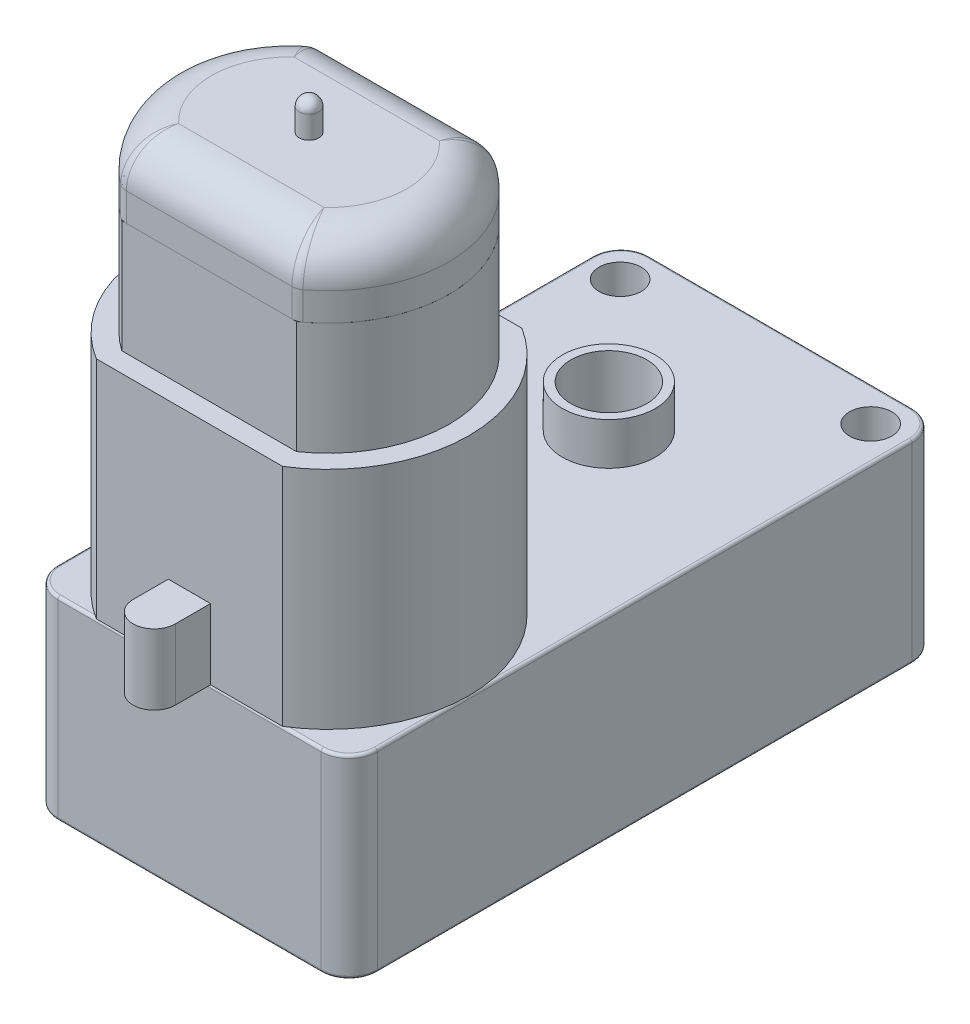
SolidWorks part; units mm, degrees
ref_plane "Front Plane" through (0, 0, 0) normal (0, 0, 1) x (1, 0, 0)
ref_plane "Top Plane" through (0, 0, 0) normal (0, 1, 0) x (1, 0, 0)
ref_plane "Right Plane" through (0, 0, 0) normal (1, 0, 0) x (0, 0, -1)
sketch "Sketch1" plane through (0, 0, 0) normal (0, 1, 0) x (1, 0, 0)
  line L1 (-11.35, -21) -> (11.35, -21)
  line L2 (-11.35, -21) -> (-11.35, 21)
  line L3 (-11.35, 21) -> (11.35, 21)
  line L4 (11.35, -21) -> (11.35, 21)
  line L5 (-11.35, -21) -> (11.35, 21) construction
  line L6 (-11.35, 21) -> (11.35, -21) construction
  point P0 (0, 0)
  dimension "D1" = 22.7
  dimension "D2" = 42
extrude "Boss-Extrude1" add sketch "Sketch1" along normal blind 13.8
sketch "Sketch2" plane through (0, 13.8, 0) normal (0, 1, 0) x (1, 0, 0)
  line L0 (-6.6178, -21) -> (6.6178, -21)
  line L1 (-11.35, -21) -> (11.35, -21) construction
  line L2 (-6.6178, -4) -> (6.6178, -4)
  line L3 (11.35, -21) -> (11.35, 21) construction
  line L4 (-11.35, 21) -> (-11.35, -21) construction
  arc A0 (6.6178, -4) -> (6.6178, -21) centre (1.35, -12.5) cw
  arc A1 (-6.6178, -4) -> (-6.6178, -21) centre (-1.35, -12.5) ccw
  point P8 (0, -4)
  point P9 (0, -21)
  dimension "D2" = 10
  dimension "D1" = 17
extrude "Boss-Extrude2" add sketch "Sketch2" along normal blind 16 separate body
sketch "Sketch3" plane through (0, 0, 0) normal (0, -1, 0) x (1, 0, 0)
  line L0 (11.35, -21) -> (-11.35, -21) construction
  circle A0 centre (0, -8.8) radius 2.7
  dimension "D1" = 5.4
  dimension "D2" = 12.2
extrude "Cut-Extrude1" cut sketch "Sketch3" against normal through all
fillet "Fillet1" radius 2 4 edges at (-11.35, 6.9, -21) (-11.35, 6.9, 21) (11.35, 6.9, 21) (11.35, 6.9, -21)
fillet "Fillet2" radius 0.2 16 edges at (0, 0, -21) (-10.7642, 0, -20.4142) (-11.35, 0, 0) (-10.7642, 0, 20.4142) (0, 0, 21) (10.7642, 0, 20.4142) (11.35, 0, 0) (10.7642, 0, -20.4142) (10.7642, 13.8, 20.4142) (0, 13.8, 21) (-10.7642, 13.8, 20.4142) (-11.35, 13.8, 0) (-10.7642, 13.8, -20.4142) (0, 13.8, -21) (10.7642, 13.8, -20.4142) (11.35, 13.8, 0)
sketch "Sketch4" plane through (0, 0, 0) normal (0, -1, 0) x (1, 0, 0)
  line L0 (8.9, -18.5) -> (-8.9, -18.5) construction
  line L1 (9.35, -21) -> (-9.35, -21) construction
  circle A0 centre (-8.9, -18.5) radius 1.5
  circle A1 centre (8.9, -18.5) radius 1.5
  point P4 (0, -18.5)
  dimension "D1" = 17.8
  dimension "D2" = 3
  dimension "D3" = 2.5
extrude "Cut-Extrude2" cut sketch "Sketch4" against normal through all
sketch "Sketch5" plane through (0, 13.8, 0) normal (0, 1, 0) x (1, 0, 0)
  circle A0 centre (0, 8.8) radius 3.3
  circle A1 centre (0, 8.8) radius 2.7 construction
  circle A2 centre (0, 8.8) radius 2.7
  dimension "D1" = 0.6
extrude "Boss-Extrude3" add sketch "Sketch5" along normal blind 3
sketch "Sketch6" plane through (0, 13.8, 0) normal (0, 1, 0) x (1, 0, 0)
  line L0 (-1.5, -21) -> (-1.5, -23.5)
  line L1 (-6.6178, -21) -> (6.6178, -21) construction
  line L2 (1.5, -23.5) -> (1.5, -21)
  line L3 (1.5, -21) -> (-1.5, -21)
  line L4 (-11.35, -12.5) -> (11.35, -12.5) construction
  line L5 (1.5, -4) -> (-1.5, -4)
  line L6 (1.5, -1.5) -> (1.5, -4)
  line L7 (-1.5, -4) -> (-1.5, -1.5)
  arc A0 (-1.5, -23.5) -> (1.5, -23.5) centre (0, -23.5) ccw
  arc A1 (-6.6178, -4) -> (-6.6178, -21) centre (-1.35, -12.5) ccw construction
  arc A2 (6.6178, -21) -> (6.6178, -4) centre (1.35, -12.5) ccw construction
  arc A3 (-1.5, -1.5) -> (1.5, -1.5) centre (0, -1.5) cw
  point P9 (0, -25)
  dimension "D1" = 4
  dimension "D2" = 2.5
extrude "Boss-Extrude4" add sketch "Sketch6" along normal blind 5
sketch "Sketch7" plane through (0, 29.8, 0) normal (0, 1, 0) x (1, 0, 0)
  line L6 (-6.2028, -19.6) -> (6.2028, -19.6)
  line L7 (6.2028, -5.4) -> (-6.2028, -5.4)
  line L8 (-6.2028, -19.6) -> (6.2028, -19.6)
  line L9 (6.2028, -5.4) -> (-6.2028, -5.4)
  arc A6 (-6.2028, -5.4) -> (-6.2028, -19.6) centre (-1.35, -12.5) ccw
  arc A7 (6.2028, -19.6) -> (6.2028, -5.4) centre (1.35, -12.5) ccw
  arc A8 (-6.2028, -5.4) -> (-6.2028, -19.6) centre (-1.35, -12.5) ccw
  arc A9 (6.2028, -19.6) -> (6.2028, -5.4) centre (1.35, -12.5) ccw
  dimension "D1" = 1.4
extrude "Boss-Extrude5" add sketch "Sketch7" along normal blind 8 separate body
sketch "Sketch8" plane through (0, 37.8, 0) normal (0, 1, 0) x (1, 0, 0)
  line L2 (-6.2028, -19.6) -> (6.2028, -19.6)
  line L3 (6.2028, -5.4) -> (-6.2028, -5.4)
  line L4 (-6.2028, -19.6) -> (6.2028, -19.6)
  line L5 (6.2028, -5.4) -> (-6.2028, -5.4)
  arc A2 (-6.2028, -5.4) -> (-6.2028, -19.6) centre (-1.35, -12.5) ccw
  arc A3 (6.2028, -19.6) -> (6.2028, -5.4) centre (1.35, -12.5) ccw
  arc A4 (-6.2028, -5.4) -> (-6.2028, -19.6) centre (-1.35, -12.5) ccw
  arc A5 (6.2028, -19.6) -> (6.2028, -5.4) centre (1.35, -12.5) ccw
  dimension "D1" = 0
extrude "Boss-Extrude6" add sketch "Sketch8" along normal blind 5 separate body
fillet "Fillet3" radius 3 4 edges at (0, 42.8, 5.4) (9.95, 42.8, 12.5) (0, 42.8, 19.6) (-9.95, 42.8, 12.5)
sketch "Sketch9" plane through (0, 0, 0) normal (1, 0, 0) x (0, 0, -1)
  line L0 (-12.5, 42.8) -> (-12.5, 45.1) construction
  line L1 (-8.4, 42.8) -> (-16.6, 42.8) construction
  line L2 (-13.2, 42.8) -> (-13.2, 44.4)
  line L3 (-13.2, 42.8) -> (-12.5, 42.8)
  line L4 (-12.5, 42.8) -> (-12.5, 45.1)
  arc A0 (-13.2, 44.4) -> (-12.5, 45.1) centre (-12.5, 44.4) cw
  dimension "D1" = 2.3
  dimension "D2" = 1.6
revolve "Revolve2" add sketch "Sketch9" angle 360 about L0
fillet "Fillet4" radius 1 8 edges at (6.2028, 38.8, 19.6) (6.0117, 41.6083, 18.9937) (6.2028, 38.8, 5.4) (-6.2028, 38.8, 5.4) (-6.2028, 38.8, 19.6) (6.0117, 41.6083, 6.0063) (-6.0117, 41.6083, 6.0063) (-6.0117, 41.6083, 18.9937)
sketch "Sketch10" plane through (0, 0, 0) normal (0, -1, 0) x (1, 0, 0)
  circle A0 centre (0, 2.1) radius 2
  circle A1 centre (0, -8.8) radius 2.7 construction
  dimension "D1" = 10.9
  dimension "D3" = 4
extrude "Boss-Extrude7" add sketch "Sketch10" along normal blind 2
